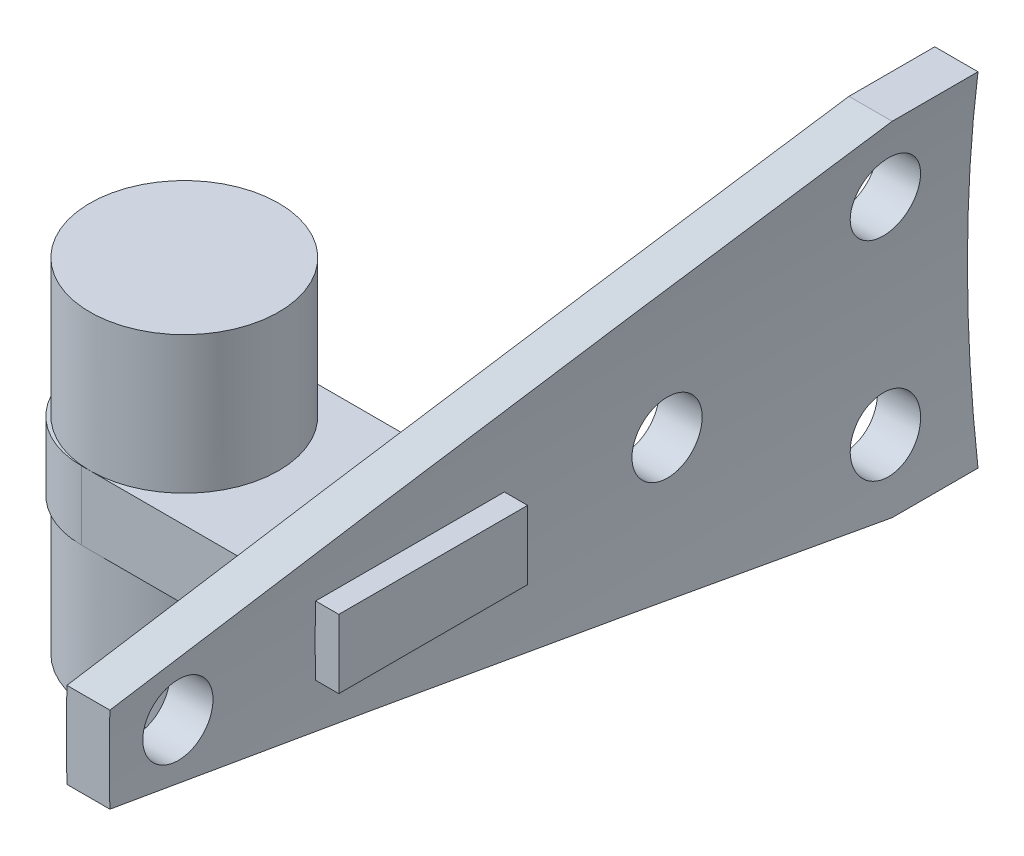
SolidWorks part; units mm, degrees
material "Plain Carbon Steel"
ref_plane "Front Plane" through (0, 0, 0) normal (0, 0, 1) x (1, 0, 0)
ref_plane "Top Plane" through (0, 0, 0) normal (0, 1, 0) x (1, 0, 0)
ref_plane "Right Plane" through (0, 0, 0) normal (1, 0, 0) x (0, 0, -1)
sketch "Sketch1" plane through (0, 0, 0) normal (0, 0, 1) x (1, 0, 0)
  line L0 (0, 0) -> (-52.4035, 0) construction
  line L1 (-83.2767, 10) -> (-80.7582, 10)
  line L2 (-83.2767, -10) -> (-80.7582, -10)
  arc A0 (-80.7582, 10) -> (-80.7582, -10) centre (0, 0) ccw
  arc A1 (-83.2767, 10) -> (-83.2767, -10) centre (0, 0) ccw
  dimension "D2" = 81.375
  dimension "D1" = 2.5
  dimension "D3" = 20
extrude "Boss-Extrude1" add sketch "Sketch1" along normal blind 50
sketch "Sketch2" plane through (0, 0, 0) normal (1, 0, 0) x (0, 0, -1)
  line L0 (0, 10) -> (0, -10)
  line L1 (0, 10) -> (-50, 10) construction
  line L2 (0, 10) -> (0, -10) construction
  line L3 (0, -10) -> (-50, -10) construction
  line L4 (-50, 10) -> (-50, -10) construction
  line L5 (0, -10) -> (-5, -10)
  line L6 (-5, -10) -> (-50, -2.5)
  line L7 (-50, -2.5) -> (-50, 2.5)
  line L8 (-50, 2.5) -> (-5, 10)
  line L9 (-5, 10) -> (0, 10)
  line L10 (0, 0) -> (-50.031, 0) construction
  line L12 (-88.7937, 27.6855) -> (20.3533, 27.6855)
  line L13 (-88.7937, 27.6855) -> (-88.7937, -33.0502)
  line L14 (-88.7937, -33.0502) -> (20.3533, -33.0502)
  line L15 (20.3533, 27.6855) -> (20.3533, -33.0502)
  dimension "D1" = 5
extrude "Cut-Extrude1" cut sketch "Sketch2" against normal through all
hole_wizard "#20 (0.161) Diameter Hole1" positions "Sketch5" profile "Sketch4" hole size "#20" standard "ANSI Inch" end condition through all
sketch "Sketch5" plane through (0, 0, 0) normal (1, 0, 0) x (0, 0, -1)
  line L1 (0, -10) -> (-42.3856, -10)
  line L2 (0, -10) -> (0, 10)
  line L3 (0, 10) -> (-42.3856, 10)
  line L4 (-42.3856, -10) -> (-42.3856, 10)
  line L7 (-5, 10) -> (0, 10) construction
  line L8 (0, 0) -> (-42.3856, 0)
  line L10 (-5, 6) -> (-5, -6)
  line L11 (-50, 2.5) -> (-50, -2.5) construction
  point P0 (-46, 0)
  point P164 (-5, 6)
  point P165 (-5, -6)
  point P172 (-5, 0)
  point P177 (-17.5, 0)
  dimension "D1" = 5
  dimension "D2" = 4
  dimension "D3" = 4
  dimension "D4" = 12.5
sketch "Sketch4" plane through (0, 0, 46) normal (0, 1, 0) x (0, 0, -1)
  line L0 (0, 0) -> (0, 83.875)
  line L1 (0, 83.875) -> (2.0447, 83.875)
  line L2 (2.0447, 83.875) -> (2.0447, 0)
  line L5 (2.0447, 0) -> (0, 0)
  line L11 (0, -6.35) -> (0, 107.95) construction
  dimension "Thru Hole Dia." = 4.0894
  dimension "Thru Hole Depth" = 83.875
ref_plane "Plane1" through (-80, 0, 0) normal (1, 0, 0) x (0, 0, -1)
sketch "Sketch7" plane through (-80, 0, -87.9998) normal (1, 0, 0) x (0, 0, -1)
  line L0 (-87.9998, 0) -> (-80.3469, 0) construction
  line L1 (-125.9998, 2) -> (-114.9998, 2)
  line L2 (-125.9998, 2) -> (-125.9998, -2)
  line L3 (-125.9998, -2) -> (-114.9998, -2)
  line L4 (-114.9998, 2) -> (-114.9998, -2)
  line L5 (-87.9998, 10) -> (-87.9998, -10) construction
  line L6 (-87.9998, -10) -> (-87.9998, 10) construction
  circle A2 centre (-133.9998, 0) radius 2.0447 construction
  point P8 (-125.9998, 0)
  dimension "D2" = 11
  dimension "D1" = 4
  dimension "D3" = 8
extrude "Boss-Extrude2" add sketch "Sketch7" against normal blind 20
fillet "Fillet1" radius 2 4 edges at (-83.8512, 2, 32.5) (-83.875, 0, 38) (-83.875, 0, 27) (-83.8512, -2, 32.5)
sketch "Sketch8" plane through (0, -2, 0) normal (0, -1, 0) x (1, 0, 0)
  line L1 (-89, 27) -> (-100, 27) construction
  line L2 (-89, 27) -> (-89, 38) construction
  line L3 (-89, 38) -> (-100, 38) construction
  line L4 (-100, 27) -> (-100, 38) construction
  line L5 (-89, 27) -> (-100, 38) construction
  line L6 (-89, 38) -> (-100, 27) construction
  circle A0 centre (-94.5, 32.5) radius 5.5
  point P0 (-94.5, 32.5)
extrude "Boss-Extrude3" add sketch "Sketch8" along normal blind 8 and the other way blind 12
fillet "Fillet2" radius 5 2 edges at (-100, 0, 38) (-100, 0, 27)
equation "\"TubeDiameter\" = 6.250in"
equation "\"D2@Sketch1\"=\"TubeDiameter\"/2+2mm"
